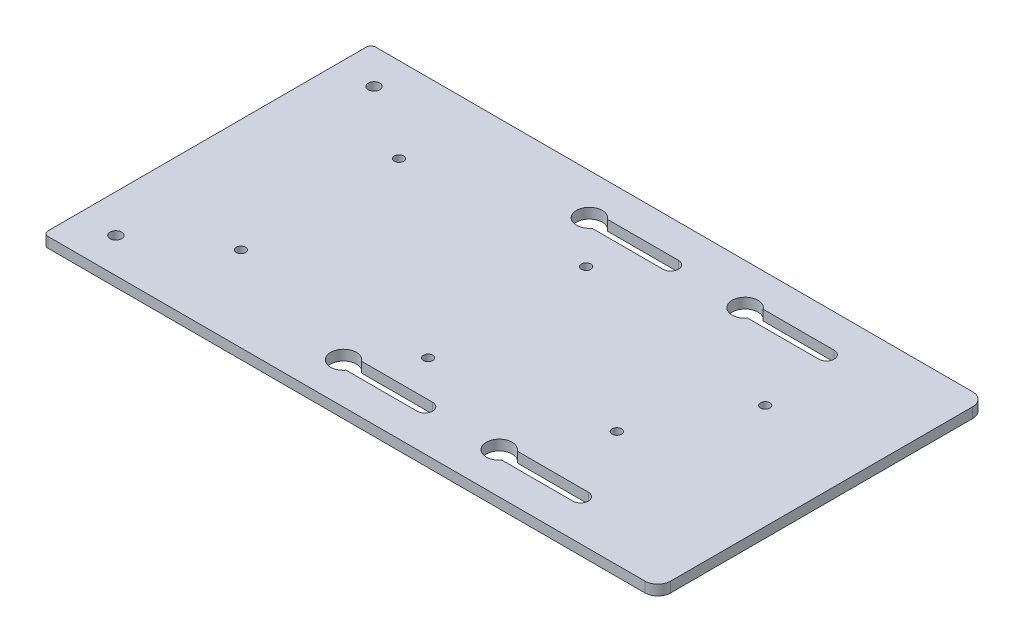
SolidWorks part; units mm, degrees
ref_plane "Front Plane" through (0, 0, 0) normal (0, 0, 1) x (1, 0, 0)
ref_plane "Top Plane" through (0, 0, 0) normal (0, 1, 0) x (1, 0, 0)
ref_plane "Right Plane" through (0, 0, 0) normal (1, 0, 0) x (0, 0, -1)
sketch "Sketch1" plane through (0, 0, 0) normal (0, 1, 0) x (1, 0, 0)
  line L0 (0, 0) -> (190.5, 0) construction
  line L1 (0, 50.8) -> (190.5, 50.8)
  line L2 (0, 50.8) -> (0, -50.8)
  line L3 (0, -50.8) -> (190.5, -50.8)
  line L4 (190.5, 50.8) -> (190.5, -50.8)
  line L5 (0, 50.8) -> (190.5, -50.8) construction
  line L6 (0, -50.8) -> (190.5, 50.8) construction
  point P0 (11.3289, 32.4526)
  point P5 (0, 0)
  dimension "D1" = 101.6
  dimension "D2" = 190.5
extrude "plate" add sketch "Sketch1" along normal blind 3.175
hole_wizard "pi holes" positions "Sketch4" profile "Sketch5" hole size "M2.5" standard "ISO" end condition through all
sketch "Sketch4" plane through (0, 3.175, 0) normal (0, 1, 0) x (1, 0, 0)
  line L0 (0, 0) -> (190.5, 0) construction
  line L1 (190.5, -50.8) -> (190.5, 50.8) construction
  line L3 (93, 24.5) -> (35, 24.5) construction
  line L5 (93, -24.5) -> (35, -24.5) construction
  line L6 (0, 50.8) -> (0, -50.8) construction
  point P0 (93, 24.5)
  point P2 (35, 24.5)
  point P18 (35, -24.5)
  point P19 (93, -24.5)
  dimension "D1" = 58
  dimension "D2" = 24.5
  dimension "D3" = 35
sketch "Sketch5" plane through (93, 3.175, -24.5) normal (1, 0, 0) x (0, 0, 1)
  line L0 (0, 0) -> (0, 3.175)
  line L1 (0, 3.175) -> (1.45, 3.175)
  line L2 (1.45, 3.175) -> (1.45, 0)
  line L5 (1.45, 0) -> (0, 0)
  line L11 (0, -6.35) -> (0, 107.95) construction
  dimension "Thru Hole Dia." = 2.9
  dimension "Thru Hole Depth" = 3.175
hole_wizard "regulator holes" positions "Sketch6" profile "Sketch7" hole size "M2.5" standard "ISO" end condition through all
sketch "Sketch6" plane through (0, 3.175, 0) normal (0, 1, 0) x (1, 0, 0)
  line L1 (0, 0) -> (190.5, 0) construction
  line L2 (190.5, -50.8) -> (190.5, 50.8) construction
  line L5 (142, -15) -> (158, -15) construction
  line L6 (142, -15) -> (142, 15) construction
  line L7 (142, 15) -> (158, 15) construction
  line L8 (158, -15) -> (158, 15) construction
  line L11 (0, 50.8) -> (0, -50.8) construction
  point P2 (158, 15)
  point P6 (142, -15)
  point P132 (142, 0)
  point P133 (158, 0)
  dimension "D1" = 16
  dimension "D2" = 30
  dimension "D3" = 142
sketch "Sketch7" plane through (158, 3.175, -15) normal (1, 0, 0) x (0, 0, 1)
  line L0 (0, 0) -> (0, 3.175)
  line L1 (0, 3.175) -> (1.45, 3.175)
  line L2 (1.45, 3.175) -> (1.45, 0)
  line L5 (1.45, 0) -> (0, 0)
  line L11 (0, -6.35) -> (0, 107.95) construction
  dimension "Thru Hole Dia." = 2.9
  dimension "Thru Hole Depth" = 3.175
hole_wizard "mount slots" positions "Sketch8" profile "Sketch9" size "M4" standard "ISO" slot yes end condition through all
sketch "Sketch8" plane through (0, 3.175, 0) normal (0, 1, 0) x (1, 0, 0)
  line L0 (93, 38.1) -> (141.26, 38.1) construction
  line L2 (0, 0) -> (190.5, 0) construction
  line L3 (190.5, -50.8) -> (190.5, 50.8) construction
  line L4 (0, 50.8) -> (0, -50.8) construction
  line L5 (93, -38.1) -> (141.26, -38.1) construction
  line L6 (78, 38.1) -> (108, 38.1) construction
  point P1 (93, 38.1)
  point P2 (141.26, 38.1)
  point P23 (141.26, -38.1)
  point P24 (93, -38.1)
  dimension "D1" = 48.26
  dimension "D2" = 38.1
  dimension "D3" = 93
  dimension "D4" = 30
sketch "Sketch9" plane through (93, 3.175, -38.1) normal (1, 0, 0) x (0, 0, 1)
  line L0 (0, 0) -> (0, 3.175)
  line L1 (0, 3.175) -> (2.4, 3.175)
  line L2 (2.4, 3.175) -> (2.4, 0)
  line L5 (2.4, 0) -> (0, 0)
  line L11 (0, -6.35) -> (0, 107.95) construction
  dimension "Thru Hole Dia." = 4.8
  dimension "Thru Hole Depth" = 3.175
sketch "Sketch12" plane through (0, 3.175, 0) normal (0, 1, 0) x (1, 0, 0)
  line L0 (-1.7463, 0) -> (1.7463, 0) construction
  circle A0 centre (128.66, 38.1) radius 4
  circle A1 centre (80.4, 38.1) radius 4
  circle A5 centre (80.4, -38.1) radius 4
  circle A6 centre (128.66, -38.1) radius 4
  arc A7 (80.4, 40.5) -> (80.4, 35.7) centre (80.4, 38.1) ccw construction
  arc A8 (128.66, 40.5) -> (128.66, 35.7) centre (128.66, 38.1) ccw construction
  dimension "D1" = 8
  dimension "D2" = 8
extrude "slot_clearance" cut sketch "Sketch12" against normal through all
hole_wizard "bracket  holes" positions "Sketch10" profile "Sketch11" hole size "M3" standard "ISO" end condition through all
sketch "Sketch10" plane through (0, 3.175, 0) normal (0, 1, 0) x (1, 0, 0)
  line L0 (0, 0) -> (190.5, 0) construction
  line L1 (0, 50.8) -> (0, -50.8) construction
  line L2 (190.5, -50.8) -> (190.5, 50.8) construction
  point P0 (11.75, 40)
  point P14 (11.75, -40)
  dimension "D1" = 11.75
  dimension "D2" = 40
sketch "Sketch11" plane through (11.75, 3.175, -40) normal (1, 0, 0) x (0, 0, 1)
  line L0 (0, 0) -> (0, 3.175)
  line L1 (0, 3.175) -> (1.8, 3.175)
  line L2 (1.8, 3.175) -> (1.8, 0)
  line L5 (1.8, 0) -> (0, 0)
  line L11 (0, -6.35) -> (0, 107.95) construction
  dimension "Thru Hole Dia." = 3.6
  dimension "Thru Hole Depth" = 3.175
fillet "back corner" radius 4 2 edges at (190.5, 1.5875, 50.8) (190.5, 1.5875, -50.8)
fillet "front corner" radius 1.5 2 edges at (0, 1.5875, -50.8) (0, 1.5875, 50.8)
